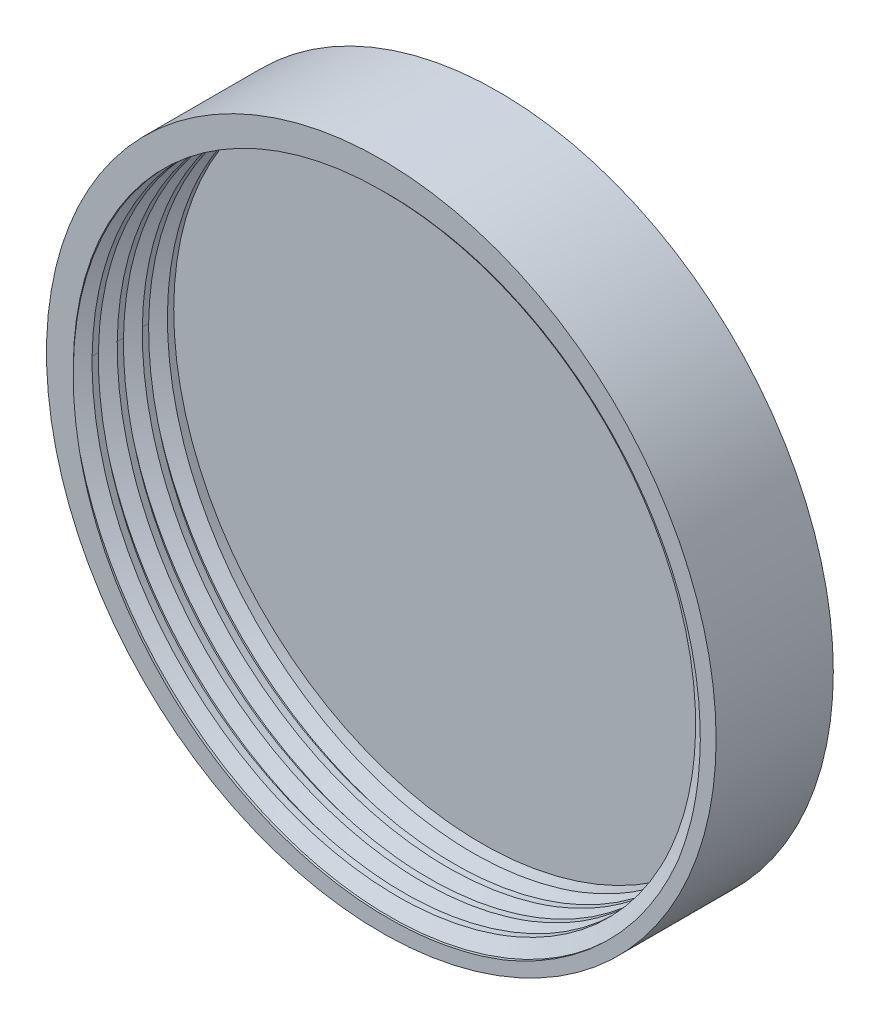
SolidWorks part; units mm, degrees
ref_plane "Piano frontale" through (0, 0, 0) normal (0, 0, 1) x (1, 0, 0)
ref_plane "Piano superiore" through (0, 0, 0) normal (0, 1, 0) x (1, 0, 0)
ref_plane "Piano destro" through (0, 0, 0) normal (1, 0, 0) x (0, 0, -1)
sketch "Schizzo1" plane through (0, 0, 0) normal (0, 0, 1) x (1, 0, 0)
  circle A0 centre (0, 0) radius 20
  dimension "D1" = 40
extrude "Estrusione-Estrusione1" add sketch "Schizzo1" along normal blind 1
sketch "Schizzo2" plane through (0, 0, 1) normal (0, 0, 1) x (1, 0, 0)
  circle A0 centre (0, 0) radius 20
  circle A1 centre (0, 0) radius 18.4
  dimension "D1" = 40
  dimension "D2" = 36.8
extrude "Estrusione-Estrusione2" add sketch "Schizzo2" along normal blind 6
thread "Filettatura1" pitch 1.5 method cut profile "Profilo filettatura1" start angle 0, offset 3, length 7.8, pitch 1.5, diameter 36.8
ref_plane "Piano1" through (-18.4, 0, 10) normal (0, -1, 0) x (-1, 0, 0)
sketch "Profilo filettatura1" plane through (-18.4, 0, 10) normal (0, -1, 0) x (-1, 0, 0)
  line L0 (0, 0) -> (0, 1.5) construction
  line L1 (0, 0) -> (0.8119, 0.4687)
  line L2 (0.8119, 0.4687) -> (0.8119, 0.6562)
  line L3 (0.8119, 0.6562) -> (0, 1.125)
  line L4 (0.8119, 0.5625) -> (0, 0.5625) construction
  line L11 (0, 0) -> (0, 1.125)
  point P2 (0, 0)
  dimension "Pitch" = 1.5
  dimension "Profile_Angle" = 60
  dimension "Profile_Land" = 0.1875
  dimension "Profile_Height" = 0.8119
